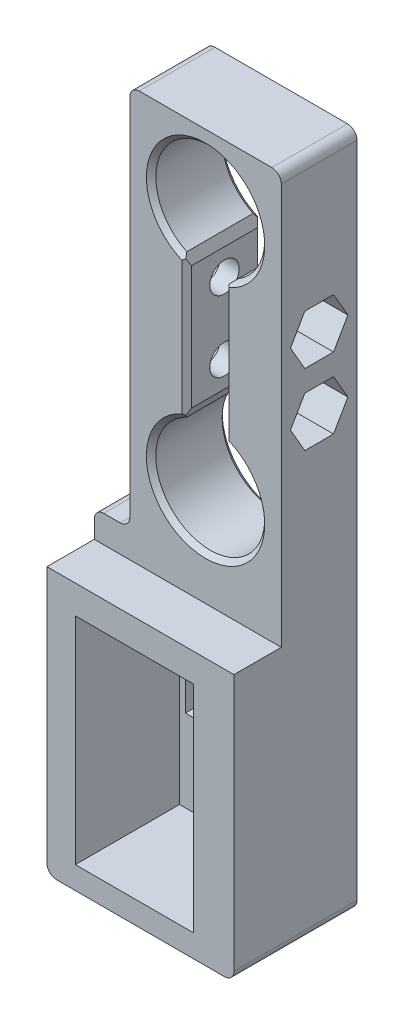
SolidWorks part; units mm, degrees
ref_plane "前视基准面" through (0, 0, 0) normal (0, 0, 1) x (1, 0, 0)
ref_plane "上视基准面" through (0, 0, 0) normal (0, 1, 0) x (1, 0, 0)
ref_plane "右视基准面" through (0, 0, 0) normal (1, 0, 0) x (0, 0, -1)
sketch "草图1" plane through (0, 0, 0) normal (0, 0, 1) x (1, 0, 0)
  line L0 (0, 51) -> (0, 0) construction
  line L1 (16, 66) -> (-16, 66)
  line L2 (-16, 66) -> (-16, -15)
  line L3 (-16, -15) -> (-23.5, -15)
  line L4 (-23.5, -15) -> (-23.5, -77)
  line L5 (-23.5, -77) -> (13.5, -77)
  line L8 (-5, -77) -> (-5, -10.7946) construction
  line L9 (13.5, -77) -> (73.5, -77)
  line L10 (-17.5, -72.25) -> (7.5, -72.25)
  line L11 (-17.5, -72.25) -> (-17.5, -26.75)
  line L12 (-17.5, -26.75) -> (7.5, -26.75)
  line L13 (7.5, -72.25) -> (7.5, -26.75)
  line L14 (-17.5, -72.25) -> (7.5, -26.75) construction
  line L15 (-17.5, -26.75) -> (7.5, -72.25) construction
  line L16 (67.5, -26.75) -> (42.5, -26.75)
  line L17 (67.5, -26.75) -> (67.5, -72.25)
  line L18 (67.5, -72.25) -> (42.5, -72.25)
  line L19 (42.5, -26.75) -> (42.5, -72.25)
  line L20 (67.5, -26.75) -> (42.5, -72.25) construction
  line L21 (67.5, -72.25) -> (42.5, -26.75) construction
  line L22 (73.5, -77) -> (73.5, -15)
  line L23 (73.5, -15) -> (16, -15)
  line L24 (16, -15) -> (16, 66)
  circle A0 centre (0, 51) radius 11.5
  circle A1 centre (0, 0) radius 11.5
  circle A2 centre (-5, -37) radius 12 construction
  circle A3 centre (55, -37) radius 48 construction
  point P15 (-5, -49.5)
  point P23 (55, -49.5)
  dimension "D1" = 23
  dimension "D2" = 23
  dimension "D3" = 51
  dimension "D6" = 15
  dimension "D8" = 37
  dimension "D12" = 12.5
  dimension "D14" = 24
  dimension "D15" = 96
  dimension "D4" = 6
  dimension "D7" = 5
  dimension "D9" = 15
  dimension "D10" = 25
  dimension "D11" = 45.5
  dimension "D13" = 62
  dimension "D16" = 45.5
  dimension "D17" = 25
  dimension "D18" = 6
extrude "凸台-拉伸1" add sketch "草图1" along normal blind 16
sketch "草图2" plane through (-16, 0, 0) normal (-1, 0, 0) x (0, 0, 1)
  line L0 (0, 25.5) -> (16, 25.5) construction
  line L3 (0, 66) -> (0, -15) construction
  line L4 (16, 66) -> (16, -15) construction
  circle A0 centre (8, 33) radius 3.1
  circle A1 centre (8, 18) radius 3.1
  dimension "D1" = 6.2
  dimension "D2" = 15
extrude "切除-拉伸1" cut sketch "草图2" against normal through all
extrude "切除-拉伸-薄壁1" cut sketch "草图2<2>" against normal blind 8 thin thin type one direction wall 2.5
sketch "草图2<2>" plane through (-16, 0, 0) normal (-1, 0, 0) x (0, 0, 1) same geometry as "草图2"
sketch "草图3" plane through (0, 0, 16) normal (0, 0, 1) x (1, 0, 0)
  line L0 (0, 51) -> (0, 0)
extrude "切除-拉伸-薄壁2" cut sketch "草图3" against normal through all and the other way through all thin thin type mid plane wall 8
sketch "草图4" plane through (16, 0, 0) normal (1, 0, 0) x (0, 0, -1)
  line L1 (-1.9378, 33) -> (-4.9689, 38.25)
  line L2 (-4.9689, 38.25) -> (-11.0311, 38.25)
  line L3 (-11.0311, 38.25) -> (-14.0622, 33)
  line L4 (-14.0622, 33) -> (-11.0311, 27.75)
  line L5 (-11.0311, 27.75) -> (-4.9689, 27.75)
  line L6 (-4.9689, 27.75) -> (-1.9378, 33)
  line L7 (-1.9378, 18) -> (-4.9689, 23.25)
  line L8 (-4.9689, 23.25) -> (-11.0311, 23.25)
  line L9 (-11.0311, 23.25) -> (-14.0622, 18)
  line L10 (-14.0622, 18) -> (-11.0311, 12.75)
  line L11 (-11.0311, 12.75) -> (-4.9689, 12.75)
  line L12 (-4.9689, 12.75) -> (-1.9378, 18)
  circle A0 centre (-8, 33) radius 5.25 construction
  circle A1 centre (-8, 18) radius 5.25 construction
  dimension "D1" = 10.5
  dimension "D2" = 10.5
extrude "切除-拉伸2" cut sketch "草图4" against normal blind 8
chamfer "倒角1" distance 1 angle 45 4 edges at (4, 40.2181, 8) (4, 10.7819, 8) (-4, 10.7819, 8) (-4, 40.2181, 8) first distance on face at (4, 25.5, 8) first distance on face at (0, -0.359, 8) first distance on face at (0, 51.359, 8)
extrude "凸台-拉伸2" add sketch "草图1<2>" along normal blind 4 contours L10 L13 L12 L11 | L16 L19 L18 L17 region at (-5, -49.5, 0) region at (55, -49.5, 0)
sketch "草图1<2>" plane through (0, 0, 0) normal (0, 0, 1) x (1, 0, 0) same geometry as "草图1"
sketch "草图6" plane through (0, 0, 4) normal (0, 0, 1) x (1, 0, 0)
  line L0 (-5, -77) -> (-5, -10.7946) construction
  line L1 (-16.25, -54.9) -> (-14.5, -54.9)
  line L2 (-16.25, -54.9) -> (-16.25, -48.5)
  line L3 (-16.25, -48.5) -> (6.25, -48.5)
  line L4 (6.25, -54.9) -> (6.25, -48.5)
  line L5 (-16.25, -54.9) -> (6.25, -48.5) construction
  line L6 (-16.25, -48.5) -> (6.25, -54.9) construction
  line L7 (-14.5, -54.9) -> (-14.5, -69.9)
  line L8 (-14.5, -69.9) -> (4.5, -69.9)
  line L9 (4.5, -69.9) -> (4.5, -54.9)
  line L10 (-5, -51.7) -> (-5, -66.9245) construction
  line L11 (4.5, -54.9) -> (6.25, -54.9)
  line L12 (7.5, -49.5) -> (42.5, -49.5) construction
  line L13 (7.5, -72.25) -> (7.5, -26.75) construction
  line L14 (42.5, -26.75) -> (42.5, -72.25) construction
  line L15 (25, -49.5) -> (25, -30.003) construction
  line L16 (55, -51.7) -> (55, -66.9245) construction
  line L17 (66.25, -48.5) -> (43.75, -54.9) construction
  line L18 (66.25, -54.9) -> (43.75, -48.5) construction
  line L19 (45.5, -54.9) -> (43.75, -54.9)
  line L20 (45.5, -69.9) -> (45.5, -54.9)
  line L21 (64.5, -69.9) -> (45.5, -69.9)
  line L22 (64.5, -54.9) -> (64.5, -69.9)
  line L23 (43.75, -54.9) -> (43.75, -48.5)
  line L24 (66.25, -48.5) -> (43.75, -48.5)
  line L25 (66.25, -54.9) -> (66.25, -48.5)
  line L26 (66.25, -54.9) -> (64.5, -54.9)
  circle A0 centre (-5, -37) radius 3.25
  circle A1 centre (55, -37) radius 3.25
  point P0 (-5, -51.7)
  dimension "D6" = 6.5
  dimension "D7" = 6.5
  dimension "D1" = 6.4
  dimension "D2" = 22.5
  dimension "D3" = 1
  dimension "D4" = 19
  dimension "D5" = 15
extrude "切除-拉伸3" cut sketch "草图6" against normal through all
sketch "草图7" plane through (0, 0, 16) normal (0, 0, 1) x (1, 0, 0)
  line L0 (-23.5, -20.75) -> (-23.5, -77)
  line L1 (-23.5, -77) -> (16, -77)
  line L2 (16, -77) -> (16, -20.75)
  line L3 (16, -15) -> (16, 66) construction
  line L4 (16, -20.75) -> (-23.5, -20.75)
  line L5 (-17.5, -26.75) -> (-17.5, -72.25)
  line L6 (-17.5, -72.25) -> (7.5, -72.25)
  line L7 (7.5, -72.25) -> (7.5, -26.75)
  line L8 (7.5, -26.75) -> (-17.5, -26.75)
  line L10 (-23.5, -77) -> (73.5, -77) construction
  line L11 (42.5, -26.75) -> (42.5, -72.25)
  line L12 (42.5, -72.25) -> (67.5, -72.25)
  line L13 (67.5, -72.25) -> (67.5, -26.75)
  line L14 (67.5, -26.75) -> (42.5, -26.75)
  line L15 (73.5, -77) -> (36.5, -77)
  line L16 (36.5, -77) -> (36.5, -20.75)
  line L17 (36.5, -20.75) -> (73.5, -20.75)
  line L18 (73.5, -77) -> (73.5, -15) construction
  line L19 (73.5, -20.75) -> (73.5, -77)
  line L20 (-23.5, -15) -> (-23.5, -77) construction
  dimension "D1" = 6
  dimension "D2" = 6
extrude "凸台-拉伸3" add sketch "草图7" along normal blind 10
fillet "圆角1" radius 2 7 edges at (-16, -15, 8) (-23.5, -15, 8) (-23.5, -77, 13) (-16, 66, 8) (73.5, -77, 13) (73.5, -15, 8) (16, 66, 8)
chamfer "倒角2" distance 1 angle 45 8 edges at (-4, 25.5, 0) (-0.5458, -11.487, 0) (4, 25.5, 0) (-0.5458, 62.487, 0) (-4, 25.5, 16) (-0.5458, -11.487, 16) (4, 25.5, 16) (-0.5458, 62.487, 16)
chamfer "倒角3" distance 25 angle 45 1 edges at (16, -15, 8)
sketch "草图8" plane through (0, 0, 16) normal (0, 0, 1) x (1, 0, 0)
  line L1 (16, 10) -> (87.3619, 10)
  line L2 (16, 10) -> (16, -84.9027)
  line L3 (16, -84.9027) -> (87.3619, -84.9027)
  line L4 (87.3619, 10) -> (87.3619, -84.9027)
extrude "切除-拉伸4" cut sketch "草图8" against normal through all both and the other way through all
fillet "圆角2" radius 2 1 edges at (16, -77, 13)
